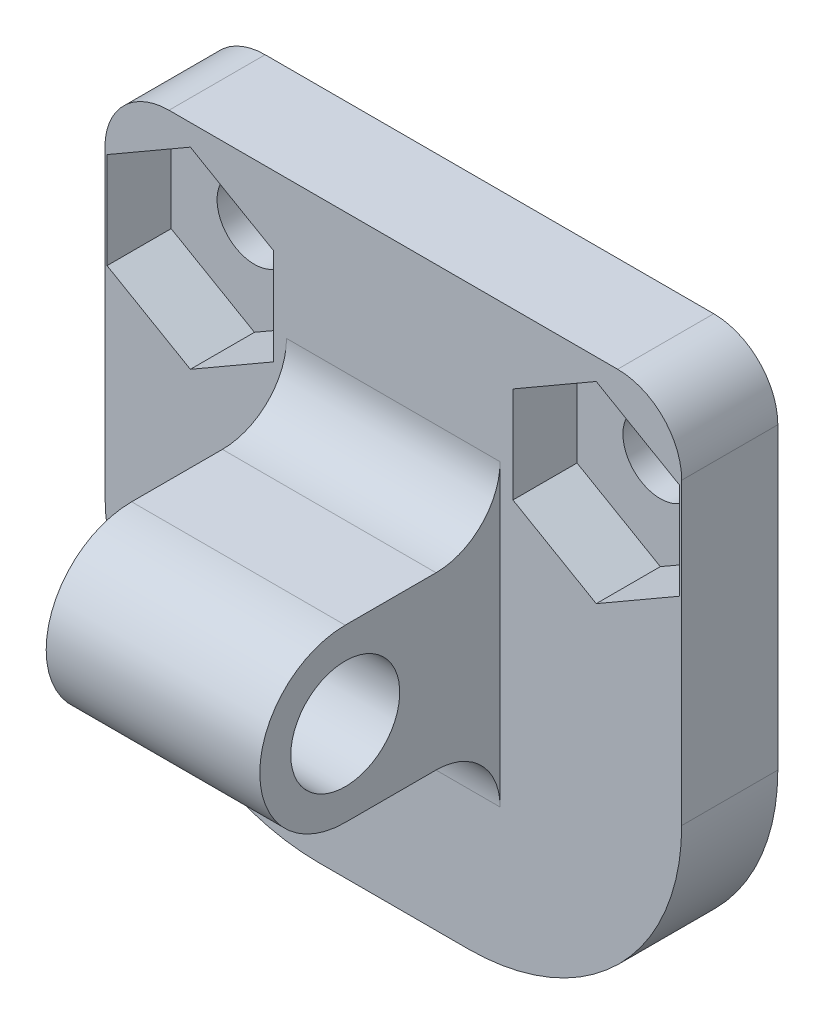
SolidWorks part; units mm, degrees
ref_plane "Front Plane" through (0, 0, 0) normal (0, 0, 1) x (1, 0, 0)
ref_plane "Top Plane" through (0, 0, 0) normal (0, 1, 0) x (1, 0, 0)
ref_plane "Right Plane" through (0, 0, 0) normal (1, 0, 0) x (0, 0, -1)
sketch "Sketch1" plane through (0, 0, 0) normal (0, 0, 1) x (1, 0, 0)
  line L0 (0, -55) -> (0, 55) construction
  line L1 (-13.5, -13.5) -> (13.5, -13.5)
  line L2 (-13.5, -13.5) -> (-13.5, 13.5)
  line L3 (-13.5, 13.5) -> (13.5, 13.5)
  line L4 (13.5, -13.5) -> (13.5, 13.5)
  line L5 (-13.5, -13.5) -> (13.5, 13.5) construction
  line L6 (-13.5, 13.5) -> (13.5, -13.5) construction
  line L8 (-5, -4) -> (5, -4)
  line L9 (-5, -4) -> (-5, 4)
  line L10 (-5, 4) -> (5, 4)
  line L11 (5, -4) -> (5, 4)
  line L12 (-5, -4) -> (5, 4) construction
  line L13 (-5, 4) -> (5, -4) construction
  circle A0 centre (-9.5, 8) radius 1.75
  circle A1 centre (9.5, 8) radius 1.75
  point P0 (0, 0)
  point P12 (0, 0)
  point P19 (0, 0)
  point P20 (0, 0)
  dimension "D5" = 3.5
  dimension "D1" = 27
  dimension "D2" = 27
  dimension "D3" = 21.5
  dimension "D4" = 4
  dimension "D6" = 8
  dimension "D7" = 10
  dimension "D9" = 13.5
extrude "Boss-Extrude1" add sketch "Sketch1" along normal blind 4.5 contours L11 L1 L4 L3 L2 L9 L10 A0 A1 | L1 L11 L10 L9 | L2 L4 L3 A0 A1 region at (-13.1182, 0, 0) region at (0, 0, 0)
extrude "Boss-Extrude2" add sketch "Sketch1<3>" along normal blind 15.75 contours L1 L11 L10 L9 region at (0, 0, 0)
sketch "Sketch1<3>" plane through (0, 0, 0) normal (0, 0, 1) x (1, 0, 0) same geometry as "Sketch1"
fillet "Fillet1" radius 10 2 edges at (13.5, -13.5, 2.25) (-13.5, -13.5, 2.25)
sketch "Sketch2" plane through (-5, 0, 0) normal (-1, 0, 0) x (0, 0, 1)
  line L0 (11.75, 4) -> (11.75, -4) construction
  line L1 (15.75, 4) -> (4.5, 4) construction
  line L3 (15.75, -4) -> (15.75, 4) construction
  line L4 (15.75, -4) -> (4.5, -4) construction
  circle A0 centre (11.75, 0) radius 2.55
  point P9 (11.75, 0)
  point P11 (0, 0)
  point P12 (0, 0)
  dimension "D2" = 5.1
  dimension "D1" = 4
extrude "Cut-Extrude1" cut sketch "Sketch2" against normal through all
fillet "Fillet2" 2 edges at (0, 4, 15.75) (0, -4, 15.75) type full round first side face at (0, 4, 10.125) second side face at (0, -4, 10.125) middle face at (0, 0, 15.75)
fillet "Fillet3" radius 3 2 edges at (0, 4, 4.5) (0, -4, 4.5)
sketch "Sketch3" plane through (0, 0, 4.5) normal (0, 0, 1) x (1, 0, 0)
  line L0 (0, -7.15) -> (0, 7.15) construction
  line L1 (-9.5, 12.5033) -> (-13.4, 10.2517)
  line L2 (-13.4, 10.2517) -> (-13.4, 5.7483)
  line L3 (-13.4, 5.7483) -> (-9.5, 3.4967)
  line L4 (-9.5, 3.4967) -> (-5.6, 5.7483)
  line L5 (-5.6, 5.7483) -> (-5.6, 10.2517)
  line L6 (-5.6, 10.2517) -> (-9.5, 12.5033)
  line L7 (5.6, 10.2517) -> (9.5, 12.5033)
  line L8 (5.6, 5.7483) -> (5.6, 10.2517)
  line L9 (9.5, 3.4967) -> (5.6, 5.7483)
  line L10 (13.4, 5.7483) -> (9.5, 3.4967)
  line L11 (13.4, 10.2517) -> (13.4, 5.7483)
  line L12 (9.5, 12.5033) -> (13.4, 10.2517)
  circle A0 centre (-9.5, 8) radius 3.9 construction
  dimension "D1" = 7.8
extrude "Cut-Extrude2" cut sketch "Sketch3" against normal blind 3
fillet "Fillet6" radius 3 2 edges at (13.5, 13.5, 2.25) (-13.5, 13.5, 2.25) tangent propagation no
